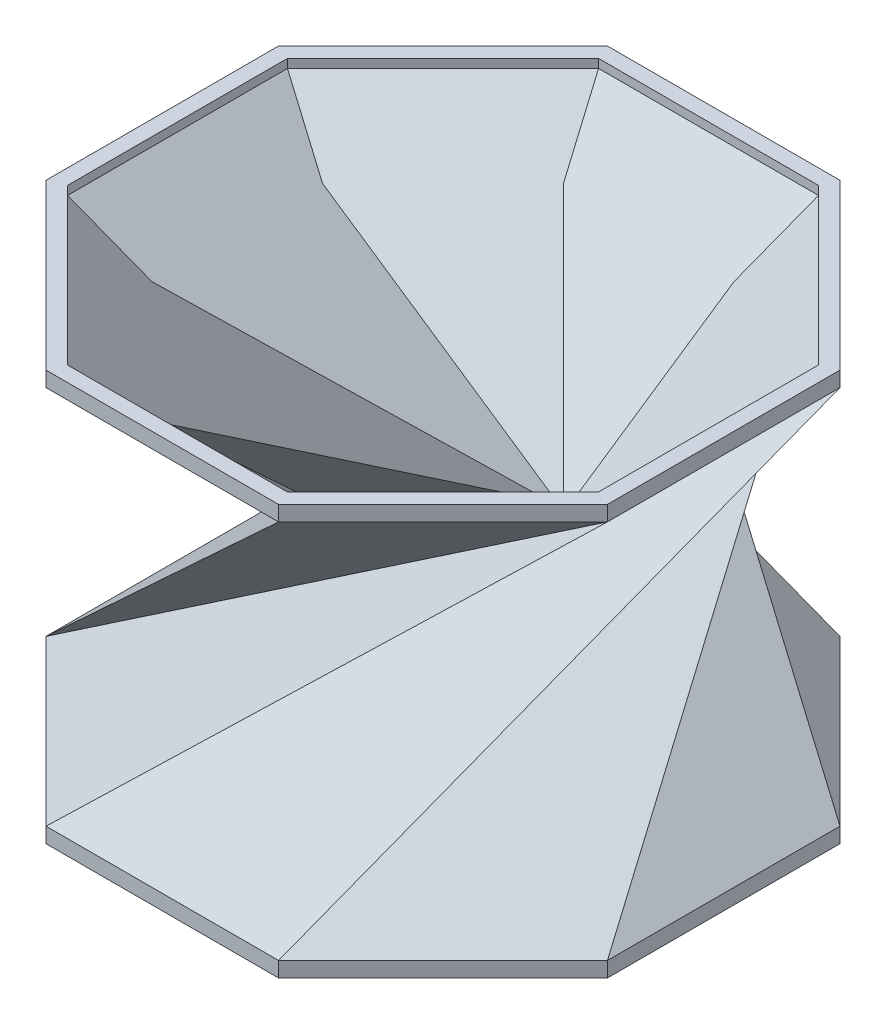
SolidWorks part; units mm, degrees
ref_plane "정면" through (0, 0, 0) normal (0, 0, 1) x (1, 0, 0)
ref_plane "윗면" through (0, 0, 0) normal (0, 1, 0) x (1, 0, 0)
ref_plane "우측면" through (0, 0, 0) normal (1, 0, 0) x (0, 0, -1)
sketch "스케치1" plane through (0, 0, 0) normal (0, 1, 0) x (1, 0, 0)
  line L0 (-55, 0) -> (55, 0) construction
  line L1 (7.6537, -18.4776) -> (18.4776, -7.6537)
  line L2 (18.4776, -7.6537) -> (18.4776, 7.6537)
  line L3 (18.4776, 7.6537) -> (7.6537, 18.4776)
  line L4 (7.6537, 18.4776) -> (-7.6537, 18.4776)
  line L5 (-7.6537, 18.4776) -> (-18.4776, 7.6537)
  line L6 (-18.4776, 7.6537) -> (-18.4776, -7.6537)
  line L7 (-18.4776, -7.6537) -> (-7.6537, -18.4776)
  line L8 (-7.6537, -18.4776) -> (7.6537, -18.4776)
  circle A0 centre (0, 0) radius 20 construction
  dimension "D1" = 40
extrude "보스-돌출1" add sketch "스케치1" along normal blind 25
ref_plane "평면1" through (0, 9.2298, 8.8302) normal (0, 0.7226, 0.6913) x (1, 0, 0)
sketch "스케치2" plane through (0, 9.2298, 8.8302) normal (0, 0.7226, 0.6913) x (1, 0, 0)
  line L0 (-7.6537, -13.3514) -> (18.4776, 22.8127)
  line L1 (18.4776, 22.8127) -> (7.6537, -13.3514)
ref_plane "평면2" through (-3.6576, 3.8231, 0) normal (-0.6913, 0.7226, 0) x (0.7226, 0.6913, 0)
sketch "스케치4" plane through (-3.6576, 3.8231, 0) normal (-0.6913, 0.7226, 0) x (0.7226, 0.6913, 0)
  line L0 (30.6338, -7.6537) -> (-5.5303, -18.4776)
ref_plane "평면3" through (-7.6537, 0, 18.4776) normal (0.5857, 0.5603, -0.5857) x (-0.7996, 0.2809, -0.5308)
sketch "스케치5" plane through (-7.6537, 0, 18.4776) normal (0.5857, 0.5603, -0.5857) x (-0.7996, 0.2809, -0.5308)
  line L0 (0, 0) -> (-12.2394, -2.034) construction
  line L1 (-8.1251, 9.3767) -> (0, 0) construction
  line L2 (0, 0) -> (-12.2394, -2.034)
  line L3 (-8.1251, 9.3767) -> (0, 0)
  line L4 (-8.1251, 9.3767) -> (-12.2394, -2.034)
extrude "컷-돌출1" cut sketch "스케치5" along normal up to vertex (44.6171 mm away) up to point (18.4776, 25, -7.6537)
pattern_circular "원형 패턴1" count 8 over 360 about axis through (0, 25, 0) along (0, 1, 0) of "컷-돌출1"
sketch "스케치7" plane through (0, 25, 0) normal (0, 1, 0) x (1, 0, 0)
  line L8 (-7.6537, -18.4776) -> (7.6537, -18.4776)
  line L9 (7.6537, -18.4776) -> (18.4776, -7.6537)
  line L10 (18.4776, -7.6537) -> (18.4776, 7.6537)
  line L11 (18.4776, 7.6537) -> (7.6537, 18.4776)
  line L12 (7.6537, 18.4776) -> (-7.6537, 18.4776)
  line L13 (-7.6537, 18.4776) -> (-18.4776, 7.6537)
  line L14 (-18.4776, 7.6537) -> (-18.4776, -7.6537)
  line L15 (-18.4776, -7.6537) -> (-7.6537, -18.4776)
  line L16 (-7.6537, -18.4776) -> (7.6537, -18.4776)
  line L17 (7.6537, -18.4776) -> (18.4776, -7.6537)
  line L18 (18.4776, -7.6537) -> (18.4776, 7.6537)
  line L19 (18.4776, 7.6537) -> (7.6537, 18.4776)
  line L20 (7.6537, 18.4776) -> (-7.6537, 18.4776)
  line L21 (-7.6537, 18.4776) -> (-18.4776, 7.6537)
  line L22 (-18.4776, 7.6537) -> (-18.4776, -7.6537)
  line L23 (-18.4776, -7.6537) -> (-7.6537, -18.4776)
  dimension "D1" = 0
extrude "보스-돌출2" add sketch "스케치7" along normal blind 1
sketch "스케치8" plane through (0, 0, 0) normal (0, -1, 0) x (1, 0, 0)
  line L8 (7.6537, 18.4776) -> (-7.6537, 18.4776)
  line L9 (-7.6537, 18.4776) -> (-18.4776, 7.6537)
  line L10 (-18.4776, 7.6537) -> (-18.4776, -7.6537)
  line L11 (-18.4776, -7.6537) -> (-7.6537, -18.4776)
  line L12 (-7.6537, -18.4776) -> (7.6537, -18.4776)
  line L13 (7.6537, -18.4776) -> (18.4776, -7.6537)
  line L14 (18.4776, -7.6537) -> (18.4776, 7.6537)
  line L15 (18.4776, 7.6537) -> (7.6537, 18.4776)
  line L16 (7.6537, 18.4776) -> (-7.6537, 18.4776)
  line L17 (-7.6537, 18.4776) -> (-18.4776, 7.6537)
  line L18 (-18.4776, 7.6537) -> (-18.4776, -7.6537)
  line L19 (-18.4776, -7.6537) -> (-7.6537, -18.4776)
  line L20 (-7.6537, -18.4776) -> (7.6537, -18.4776)
  line L21 (7.6537, -18.4776) -> (18.4776, -7.6537)
  line L22 (18.4776, -7.6537) -> (18.4776, 7.6537)
  line L23 (18.4776, 7.6537) -> (7.6537, 18.4776)
  dimension "D1" = 0
extrude "보스-돌출3" add sketch "스케치8" along normal blind 1
shell "쉘1" thickness 1 removed face at (0, -1, 0) removed face at (0, 26, 0)
